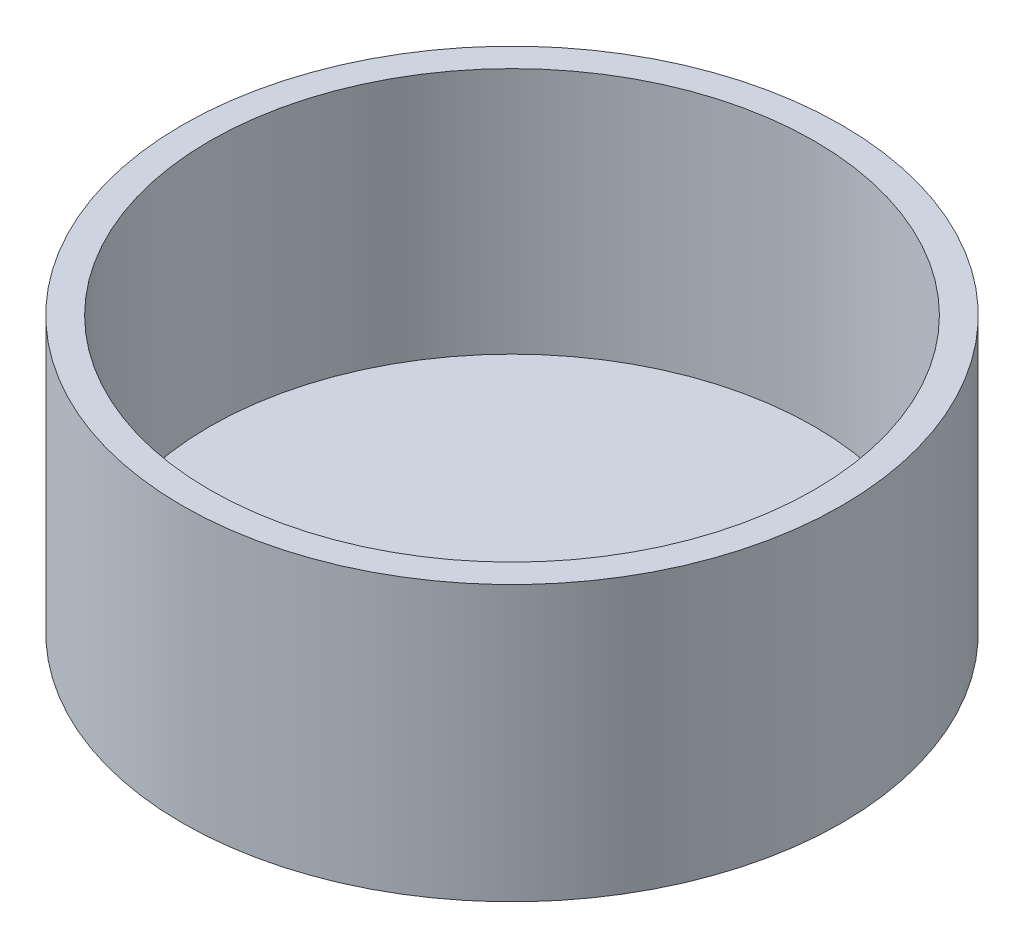
SolidWorks part; units mm, degrees
ref_plane "Front Plane" through (0, 0, 0) normal (0, 0, 1) x (1, 0, 0)
ref_plane "Top Plane" through (0, 0, 0) normal (0, 1, 0) x (1, 0, 0)
ref_plane "Right Plane" through (0, 0, 0) normal (1, 0, 0) x (0, 0, -1)
sketch "Sketch1" plane through (0, 0, 0) normal (0, 1, 0) x (1, 0, 0)
  line L1 (-20.6375, -20.6375) -> (20.6375, -20.6375)
  line L2 (-20.6375, -20.6375) -> (-20.6375, 20.6375)
  line L3 (-20.6375, 20.6375) -> (20.6375, 20.6375)
  line L4 (20.6375, -20.6375) -> (20.6375, 20.6375)
  line L5 (-20.6375, -20.6375) -> (20.6375, 20.6375) construction
  line L6 (-20.6375, 20.6375) -> (20.6375, -20.6375) construction
  circle A0 centre (0, 0) radius 139.7
  circle A1 centre (0, 0) radius 152.4
  point P0 (0, 0)
  dimension "D3" = 279.4
  dimension "D4" = 304.8
  dimension "D1" = 41.275
  dimension "D2" = 41.275
extrude "Boss-Extrude2" add sketch "Sketch1" along normal blind 127 contours A1 A0 region at (-148.0895, 0, 0)
extrude "Boss-Extrude3" add sketch "Sketch1<7>" along normal blind 12.7 contours A0
sketch "Sketch1<7>" plane through (0, 0, 0) normal (0, 1, 0) x (1, 0, 0) same geometry as "Sketch1"
